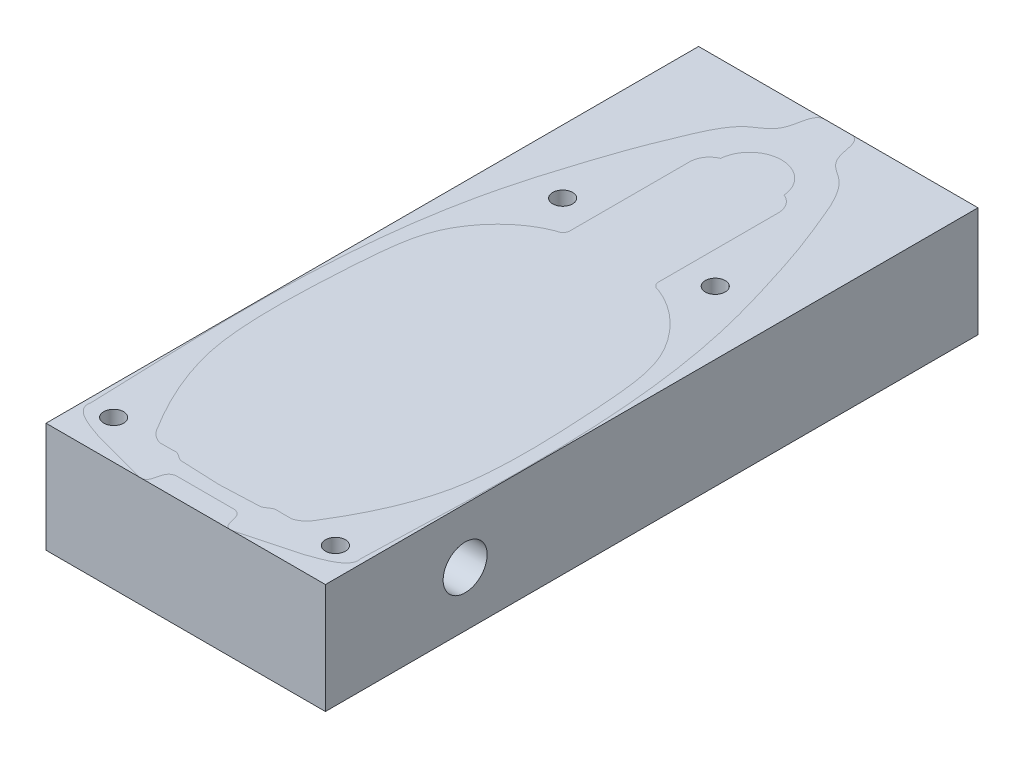
SolidWorks part; units mm, degrees
material "McMaster 6061-T6"
ref_plane "Front" through (0, 0, 0) normal (0, 0, 1) x (1, 0, 0)
ref_plane "Top" through (0, 0, 0) normal (0, 1, 0) x (1, 0, 0)
ref_plane "Right" through (0, 0, 0) normal (1, 0, 0) x (0, 0, -1)
sketch "Sketch1" plane through (0, 0, 0) normal (0, 1, 0) x (1, 0, 0)
  line L1 (-50.8, 217.4425) -> (50.8, 217.4425)
  line L2 (-50.8, 217.4425) -> (-50.8, -19.8419)
  line L3 (-50.8, -19.8419) -> (50.8, -19.8419)
  line L4 (50.8, 217.4425) -> (50.8, -19.8419)
  point P0 (0, 0)
  point P1 (0, 217.4425)
  line B0 (-57.2666, 0) -> (300.4907, 0) construction
  line B1 (58.0403, 1359.2193) -> (751.3736, 1359.2193) construction
  line B2 (0, 184.9685) -> (0, 135.7325) construction
  line B3 (-16.1045, 179.4899) -> (-16.1045, 135.5349)
  line B4 (-23.9297, -5.2923) -> (-19.0013, -5.2923)
  line B5 (-14.3059, -7.1081) -> (0, -7.7134)
  line B6 (4.4455, 217.4425) -> (-4.4455, 217.4425)
  line B7 (-10.5714, -12.7274) -> (10.5714, -12.7274)
  line B8 (14.3059, -7.1081) -> (0, -7.7134)
  line B9 (23.9297, -5.2923) -> (19.0013, -5.2923)
  line B10 (16.1045, 179.4899) -> (16.1045, 135.5349)
  arc B11 (11.5473, 186.1748) -> (-11.5473, 186.1748) centre (0, 185.2223) ccw
  arc B12 (-11.5473, 186.1748) -> (-16.1045, 179.4899) centre (-8.9229, 179.4899) ccw
  arc B13 (-16.1045, 135.5349) -> (-18.7447, 133.3526) centre (-19.0013, 136.3511) cw
  arc B14 (16.1045, 135.5349) -> (18.7447, 133.3526) centre (19.0013, 136.3511) ccw
  arc B15 (11.5473, 186.1748) -> (16.1045, 179.4899) centre (8.9229, 179.4899) cw
  circle B16 centre (-27.745, 144.9525) radius 3.6247
  circle B17 centre (-40.3206, -5.716) radius 3.6247
  circle B18 centre (40.3206, -5.716) radius 3.6247
  circle B19 centre (27.745, 144.9525) radius 3.6247
  spline B20 degree 3 poles (-18.7447, 133.3526) (-24.0724, 131.2924) (-32.603, 124.9988) (-41.6376, 111.3739) (-43.9656, 96.1245) (-45.0501, 79.5297) (-45.8816, 62.8086) (-45.6029, 47.686) (-43.2164, 25.6573) (-35.9471, 10.0985) (-28.9898, -1.1126) knots 0 0 0 0 0.114752 0.211975 0.323248 0.422595 0.550935 0.662789 0.729557 1 1 1 1
  spline B21 degree 3 poles (-28.9898, -1.1126) (-27.9742, -3.0999) (-26.1032, -4.7308) (-23.9297, -5.2923) knots 0 0 0 0 1 1 1 1
  spline B22 degree 3 poles (-19.0013, -5.2923) (-16.9934, -4.8476) (-16.0767, -6.8562) (-14.3059, -7.1081) knots 0 0 0 0 1 1 1 1
  spline B23 degree 3 poles (-4.4455, 217.4425) (-6.5665, 217.6433) (-8.2866, 214.6032) (-8.8185, 209.8097) (-10.4503, 205.542) (-13.9883, 202.8783) (-17.1351, 200.8787) (-21.9225, 195.1985) (-25.1053, 187.0236) (-30.5496, 174.0979) (-35.9601, 157.7735) (-44.7383, 128.666) (-52.5309, 73.6432) (-50.0644, 26.1167) (-49.0771, -5.2923) knots 0 0 0 0 0.022097 0.039559 0.063259 0.077264 0.095563 0.110967 0.171488 0.206517 0.29131 0.391743 0.596457 1 1 1 1
  spline B24 degree 3 poles (-49.0771, -5.2923) (-50.5689, -10.9401) (-38.8329, -13.5043) (-37.4191, -14.3419) knots 0 0 0 0 1 1 1 1
  spline B25 degree 1 poles (-37.4191, -14.3419) (-18.3852, -19.4149) knots 0 0 1 1
  spline B26 degree 3 poles (-18.3852, -19.4149) (-11.6134, -21.8049) (-15.7198, -13.4118) (-10.5714, -12.7274) knots 0 0 0 0 1 1 1 1
  spline B27 degree 3 poles (18.3852, -19.4149) (11.6134, -21.8049) (15.7198, -13.4118) (10.5714, -12.7274) knots 0 0 0 0 1 1 1 1
  spline B28 degree 1 poles (37.4191, -14.3419) (18.3852, -19.4149) knots 0 0 1 1
  spline B29 degree 3 poles (49.0771, -5.2923) (50.5689, -10.9401) (38.8329, -13.5043) (37.4191, -14.3419) knots 0 0 0 0 1 1 1 1
  spline B30 degree 3 poles (4.4455, 217.4425) (6.5665, 217.6433) (8.2866, 214.6032) (8.8185, 209.8097) (10.4503, 205.542) (13.9883, 202.8783) (17.1351, 200.8787) (21.9225, 195.1985) (25.1053, 187.0236) (30.5496, 174.0979) (35.9601, 157.7735) (44.7383, 128.666) (52.5309, 73.6432) (50.0644, 26.1167) (49.0771, -5.2923) knots 0 0 0 0 0.022097 0.039559 0.063259 0.077264 0.095563 0.110967 0.171488 0.206517 0.29131 0.391743 0.596457 1 1 1 1
  spline B31 degree 3 poles (19.0013, -5.2923) (16.9934, -4.8476) (16.0767, -6.8562) (14.3059, -7.1081) knots 0 0 0 0 1 1 1 1
  spline B32 degree 3 poles (28.9898, -1.1126) (27.9742, -3.0999) (26.1032, -4.7308) (23.9297, -5.2923) knots 0 0 0 0 1 1 1 1
  spline B33 degree 3 poles (18.7447, 133.3526) (24.0724, 131.2924) (32.603, 124.9988) (41.6376, 111.3739) (43.9656, 96.1245) (45.0501, 79.5297) (45.8816, 62.8086) (45.6029, 47.686) (43.2164, 25.6573) (35.9471, 10.0985) (28.9898, -1.1126) knots 0 0 0 0 0.114752 0.211975 0.323248 0.422595 0.550935 0.662789 0.729557 1 1 1 1
  dimension "D1" = 101.6
  dimension "D2" = 237.2844
sketch_block_instance "Block-RoughDrillPressMounting-1"
sketch_block "Block-RoughDrillPressMounting"
extrude "Boss-Extrude1" add sketch "Sketch1" against normal blind 39.9999 contours B26 B25 B24 B23 L1 L2 L3 | L1 B30 B29 B28 B27 L3 L4 | B30 L1 B23 B24 B25 B26 B7 B27 B28 B29 B18 B17 B16 B19 B14 B33 B32 B9 B31 B8 B5 B22 B4 B21 B20 B13 B3 B12 B11 B15 B10 | B33 B14 B10 B15 B11 B12 B3 B13 B20 B21 B4 B22 B5 B8 B31 B9 B32 | L3 B27 B7 B26 region at (0, 0, -214.8633) region at (-38.3174, 0, -161.5358) region at (38.3167, 0, -161.5392) region at (0, 0, 16.4213) region at (0, 0, -77.7954)
sketch "Sketch2" plane through (-50.8, 0, 0) normal (-1, 0, 0) x (0, 0, 1)
  line L1 (-217.4425, 0) -> (19.8419, 0) construction
  line L2 (19.8419, -39.9999) -> (19.8419, 0) construction
  circle A0 centre (-30.9581, -20) radius 8
  line B0 (-17.6916, 0) -> (-44.2246, 0)
  line B1 (-44.2246, -40) -> (-17.6916, -40)
  arc B2 (-44.2246, 0) -> (-44.2246, -40) centre (-30.9581, -20) ccw
  arc B3 (-17.6916, -40) -> (-17.6916, 0) centre (-30.9581, -20) ccw
  arc B4 (-30.9581, -6) -> (-30.9581, -34) centre (-30.9581, -20) ccw
  arc B5 (-30.9581, -34) -> (-30.9581, -6) centre (-30.9581, -20) ccw
  arc B6 (-17.5231, -36.185) -> (-17.5231, -30.685) centre (-17.5231, -33.435) ccw
  arc B7 (-17.5231, -30.685) -> (-17.5231, -36.185) centre (-17.5231, -33.435) ccw
  arc B8 (-11.9581, -22.75) -> (-11.9581, -17.25) centre (-11.9581, -20) ccw
  arc B9 (-11.9581, -17.25) -> (-11.9581, -22.75) centre (-11.9581, -20) ccw
  arc B10 (-17.5231, -9.315) -> (-17.5231, -3.815) centre (-17.5231, -6.565) ccw
  arc B11 (-17.5231, -3.815) -> (-17.5231, -9.315) centre (-17.5231, -6.565) ccw
  arc B12 (-44.3932, -36.185) -> (-44.3932, -30.685) centre (-44.3932, -33.435) ccw
  arc B13 (-44.3932, -30.685) -> (-44.3932, -36.185) centre (-44.3932, -33.435) ccw
  arc B14 (-49.9581, -22.75) -> (-49.9581, -17.25) centre (-49.9581, -20) ccw
  arc B15 (-49.9581, -17.25) -> (-49.9581, -22.75) centre (-49.9581, -20) ccw
  arc B16 (-44.3932, -9.315) -> (-44.3932, -3.815) centre (-44.3932, -6.565) ccw
  arc B17 (-44.3932, -3.815) -> (-44.3932, -9.315) centre (-44.3932, -6.565) ccw
  dimension "D2" = 16
  dimension "D1" = 50.8
sketch_block_instance "Block-Screw Nut Mount-1"
sketch_block "Block-Screw Nut Mount"
extrude "Cut-Extrude1" cut sketch "Sketch2" against normal blind 12.7 contours B16 B17 | B14 B15 | B12 B13 | B6 B7 | B8 B9 | B10 B11 region at (-50.8, -33.435, -17.5231) region at (-50.8, -20, -11.9581) region at (-50.8, -6.565, -17.5231) region at (-50.8, -33.435, -44.3932) region at (-50.8, -20, -49.9581) region at (-50.8, -6.565, -44.3932)
extrude "Cut-Extrude2" cut sketch "Sketch2<5>" against normal blind 32 contours B4 B5 | A0 region at (-50.8, -20, -30.9581) region at (-50.8, -20, -17.3541)
sketch "Sketch2<5>" plane through (-50.8, 0, 0) normal (-1, 0, 0) x (0, 0, 1) same geometry as "Sketch2"
extrude "Cut-Extrude3" cut sketch "Sketch2<6>" against normal through all contours A0 region at (-50.8, -20, -30.9581)
sketch "Sketch2<6>" plane through (-50.8, 0, 0) normal (-1, 0, 0) x (0, 0, 1) same geometry as "Sketch2"
sketch "Sketch3" plane through (0, -39.9999, 0) normal (0, -1, 0) x (1, 0, 0)
  line L0 (-50.8, -217.4425) -> (-50.8, 19.8419) construction
  point P2 (-50.8, -30.9581)
  point P13 (-50.8, -30.9581)
  line B0 (-50.8, -17.6916) -> (-50.8, -44.2246)
  arc B1 (-18.219, -12.5581) -> (-18.219, -8.3581) centre (-18.219, -10.4581) ccw
  arc B2 (-18.219, -8.3581) -> (-18.219, -12.5581) centre (-18.219, -10.4581) ccw
  arc B3 (-44.219, -12.5581) -> (-44.219, -8.3581) centre (-44.219, -10.4581) ccw
  arc B4 (-44.219, -8.3581) -> (-44.219, -12.5581) centre (-44.219, -10.4581) ccw
  arc B5 (-18.219, -53.5581) -> (-18.219, -49.3581) centre (-18.219, -51.4581) ccw
  arc B6 (-18.219, -49.3581) -> (-18.219, -53.5581) centre (-18.219, -51.4581) ccw
  arc B7 (-44.219, -53.5581) -> (-44.219, -49.3581) centre (-44.219, -51.4581) ccw
  arc B8 (-44.219, -49.3581) -> (-44.219, -53.5581) centre (-44.219, -51.4581) ccw
sketch_block_instance "Block-Carriage Mount-1"
sketch_block "Block-Carriage Mount"
extrude "Cut-Extrude4" cut sketch "Sketch3" against normal blind 6.35 contours B7 B8 | B5 B6 | B1 B2 | B3 B4 region at (-18.219, -39.9999, -10.4581) region at (-44.219, -39.9999, -10.4581) region at (-18.219, -39.9999, -51.4581) region at (-44.219, -39.9999, -51.4581)
sketch "Sketch4" plane through (0, -39.9999, 0) normal (0, -1, 0) x (1, 0, 0)
  line L0 (-50.8, -217.4425) -> (-50.8, 19.8419) construction
  line L1 (-50.8, -57.0242) -> (-12.2477, -57.0242)
  line L2 (-50.8, -57.0242) -> (-50.8, -4.2879)
  line L3 (-50.8, -4.2879) -> (-12.2477, -4.2879)
  line L4 (-12.2477, -57.0242) -> (-12.2477, -4.2879)
split line "Split Line1"
sketch "Sketch5" plane through (0, -39.9999, 0) normal (0, -1, 0) x (1, 0, 0)
  line L0 (0, 19.8419) -> (0, 121.4419)
  line L1 (-50.8, 19.8419) -> (50.8, 19.8419) construction
  circle A0 centre (0, 121.4419) radius 24.6832
  dimension "D1" = 101.6
sketch "Sketch6" plane through (0, 0, 0) normal (0, 1, 0) x (1, 0, 0)
  line L0 (50.8, 217.4425) -> (-50.8, -19.8419)
  point P2 (0, 98.8003)
ref_point "Point1"
split line "Split Line2"
sketch "Sketch1<3>" plane through (0, 0, 0) normal (0, 1, 0) x (1, 0, 0) same geometry as "Sketch1"
